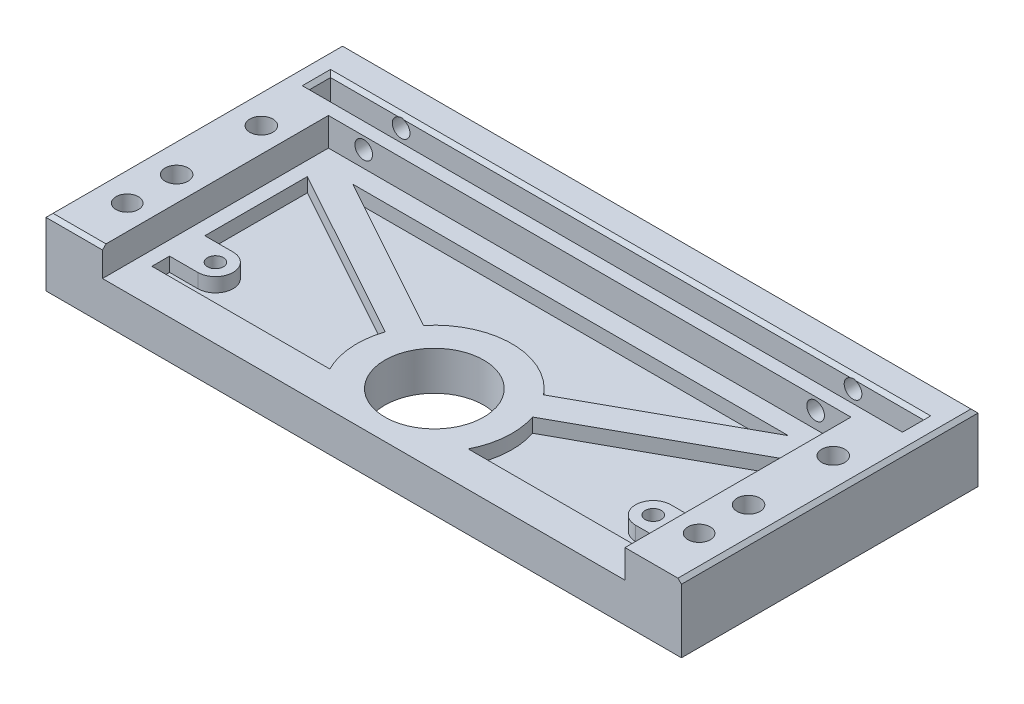
SolidWorks part; units mm, degrees
ref_plane "Front Plane" through (0, 0, 0) normal (0, 0, 1) x (1, 0, 0)
ref_plane "Top Plane" through (0, 0, 0) normal (0, 1, 0) x (1, 0, 0)
ref_plane "Right Plane" through (0, 0, 0) normal (1, 0, 0) x (0, 0, -1)
sketch "Sketch1" plane through (0, 0, 0) normal (0, 0, 1) x (1, 0, 0)
  line L1 (0, 0) -> (90, 0)
  line L2 (0, 0) -> (0, 9.525)
  line L3 (0, 9.525) -> (90, 9.525)
  line L4 (90, 0) -> (90, 9.525)
  circle A0 centre (30, 4.7625) radius 2
  circle A1 centre (60, 4.7625) radius 2
  point P7 (0, 4.7625)
  point P11 (45, 0)
  dimension "D5" = 4
  dimension "D1" = 90
  dimension "D2" = 9.525
  dimension "D3" = 15
  dimension "D4" = 15
extrude "Boss-Extrude1" add sketch "Sketch1" along normal blind 45 contours A1 | A0 | L1 L4 L3 L2 A1 A0
sketch "Sketch2" plane through (0, 9.525, 0) normal (0, 1, 0) x (1, 0, 0)
  line L0 (0, 0) -> (90, 0) construction
  circle A0 centre (45, -35) radius 7
  point P4 (45, 0)
  dimension "D2" = 14
  dimension "D1" = 35
extrude "Cut-Extrude2" cut sketch "Sketch2" against normal blind 10
sketch "Sketch3" plane through (0, 9.525, 0) normal (0, 1, 0) x (1, 0, 0)
  line L0 (90, -45) -> (90, 0) construction
  line L1 (0, -45) -> (0, 0) construction
  circle A0 centre (85.5, -31) radius 1.632
  circle A1 centre (4.5, -31) radius 1.632
  circle A2 centre (45, -35) radius 7 construction
  circle A3 centre (45, -35) radius 7
  circle A4 centre (85.5, -19) radius 1.632
  circle A5 centre (4.5, -19) radius 1.632
  circle A6 centre (76, -35) radius 1.1303
  circle A7 centre (14, -35) radius 1.1303
  dimension "D1" = 3.2639
  dimension "D8" = 31
  dimension "D9" = 2.2606
  dimension "D2" = 4.5
  dimension "D3" = 4.5
  dimension "D5" = 12
  dimension "D6" = 4
  dimension "D7" = 31
  dimension "D4" = 2
extrude "Cut-Extrude3" cut sketch "Sketch3" against normal blind 10
sketch "Sketch4" plane through (0, 9.525, 0) normal (0, 1, 0) x (1, 0, 0)
  line L1 (87, -7.7) -> (3, -7.7)
  line L2 (87, -7.7) -> (87, -10.7)
  line L3 (87, -10.7) -> (3, -10.7)
  line L4 (3, -7.7) -> (3, -10.7)
  line L6 (90, -45) -> (90, 0) construction
  line L7 (0, -45) -> (0, 0) construction
  circle A0 centre (45, -35) radius 7 construction
  dimension "D1" = 24.3
  dimension "D2" = 3
  dimension "D3" = 3
  dimension "D4" = 3
extrude "Cut-Extrude4" cut sketch "Sketch4" against normal blind 6
sketch "Sketch6" plane through (0, 9.525, 0) normal (0, 1, 0) x (1, 0, 0)
  line L0 (14, -37.5) -> (10, -37.5)
  line L1 (14, -32.5) -> (10, -32.5)
  line L2 (76, -37.5) -> (80, -37.5)
  line L3 (76, -32.5) -> (80, -32.5)
  line L4 (80, -32.5) -> (80, -15.7)
  line L5 (54.798, -40) -> (80, -40)
  line L6 (80, -40) -> (80, -37.5)
  line L7 (80, -15.7) -> (10, -15.7)
  line L8 (10, -15.7) -> (10, -32.5)
  line L9 (90, -45) -> (90, 0)
  line L10 (90, 0) -> (0, 0)
  line L11 (0, 0) -> (0, -45)
  line L12 (0, -45) -> (90, -45)
  line L13 (90, -45) -> (90, 0)
  line L15 (0, 0) -> (0, -45)
  line L16 (0, -45) -> (90, -45)
  line L17 (10, -40) -> (35.202, -40)
  line L18 (3, -10.7) -> (87, -10.7) construction
  line L19 (80, -15.7) -> (45, -35) construction
  line L20 (45, -35) -> (10, -15.7) construction
  line L21 (80, -17.9839) -> (55.4378, -31.5282)
  line L22 (75.8582, -15.7) -> (53.5062, -28.0255)
  line L23 (36.4938, -28.0255) -> (14.1418, -15.7)
  line L24 (34.5622, -31.5282) -> (10, -17.9839)
  line L25 (10, -37.5) -> (10, -40)
  line L29 (90, 0) -> (0, 0)
  arc A0 (14, -37.5) -> (14, -32.5) centre (14, -35) ccw
  circle A1 centre (45, -35) radius 11
  arc A2 (76, -32.5) -> (76, -37.5) centre (76, -35) ccw
  dimension "D2" = 22
  dimension "D11" = 5
  dimension "D12" = 5
  dimension "D3" = 5
  dimension "D4" = 10
  dimension "D5" = 5
  dimension "D6" = 10
  dimension "D7" = 2
  dimension "D8" = 4
  dimension "D9" = 2
  dimension "D10" = 4
  dimension "D1" = 0
extrude "Cut-Extrude6" cut sketch "Sketch6" against normal blind 6 and the other way through all contours A1 L5 L6 L21 | A1 L22 L7 L23 | A1 L24 L8 L17
sketch "Sketch7" plane through (0, 9.525, 0) normal (0, 1, 0) x (1, 0, 0)
  line L0 (0, -45) -> (0, 0) construction
  line L1 (90, 0) -> (0, 0)
  line L2 (90, 0) -> (90, -3)
  line L3 (90, -3) -> (0, -3)
  line L4 (0, 0) -> (0, -3)
  dimension "D1" = 3
extrude "Cut-Extrude7" cut sketch "Sketch7" against normal blind 10
sketch "Sketch9" plane through (0, 9.525, 0) normal (0, 1, 0) x (1, 0, 0)
  line L0 (0, -45) -> (90, -45) construction
  line L1 (82, -45) -> (8, -45)
  line L2 (82, -45) -> (82, -13)
  line L3 (82, -13) -> (8, -13)
  line L4 (8, -45) -> (8, -13)
  line L5 (90, -45) -> (90, -3) construction
  line L6 (0, -45) -> (0, -3) construction
  line L7 (0, -3) -> (90, -3) construction
  dimension "D1" = 8
  dimension "D2" = 8
  dimension "D3" = 10
extrude "Cut-Extrude8" cut sketch "Sketch9" against normal blind 4
sketch "Sketch10" plane through (0, 0, 13) normal (0, 0, 1) x (1, 0, 0)
  line L0 (82, 5.525) -> (82, 9.525) construction
  line L1 (8, 5.525) -> (8, 9.525) construction
  line L2 (82, 9.525) -> (8, 9.525) construction
  circle A0 centre (77, 7.825) radius 1.25
  circle A1 centre (13, 7.825) radius 1.25
  dimension "D1" = 2.5
  dimension "D2" = 5
  dimension "D3" = 5
  dimension "D4" = 1.7
extrude "Cut-Extrude9" cut sketch "Sketch10" against normal up to surface (10 mm away) up to face at (45, 4.7625, 3)
chamfer "Chamfer2" distance 0.5 angle 45 7 edges at (45, 9.525, 3) (87, 9.525, 9.2) (45, 9.525, 7.7) (3, 9.525, 9.2) (45, 9.525, 10.7) (0, 9.525, 24) (90, 9.525, 24)
sketch "Sketch11" plane through (0, 9.525, 0) normal (0, 1, 0) x (1, 0, 0)
  circle A0 centre (85.5, -38) radius 1.5875
  circle A1 centre (85.5, -31) radius 1.632 construction
  circle A2 centre (85.5, -31) radius 1.632
  circle A3 centre (4.5, -38) radius 1.5875
  circle A4 centre (4.5, -31) radius 1.632 construction
  circle A5 centre (4.5, -31) radius 1.632
  point P10 (0, 0)
  point P11 (0, 0)
  dimension "D2" = 3.175
  dimension "D1" = 7
extrude "Cut-Extrude10" cut sketch "Sketch11" against normal blind 4 contours A0 | A3
